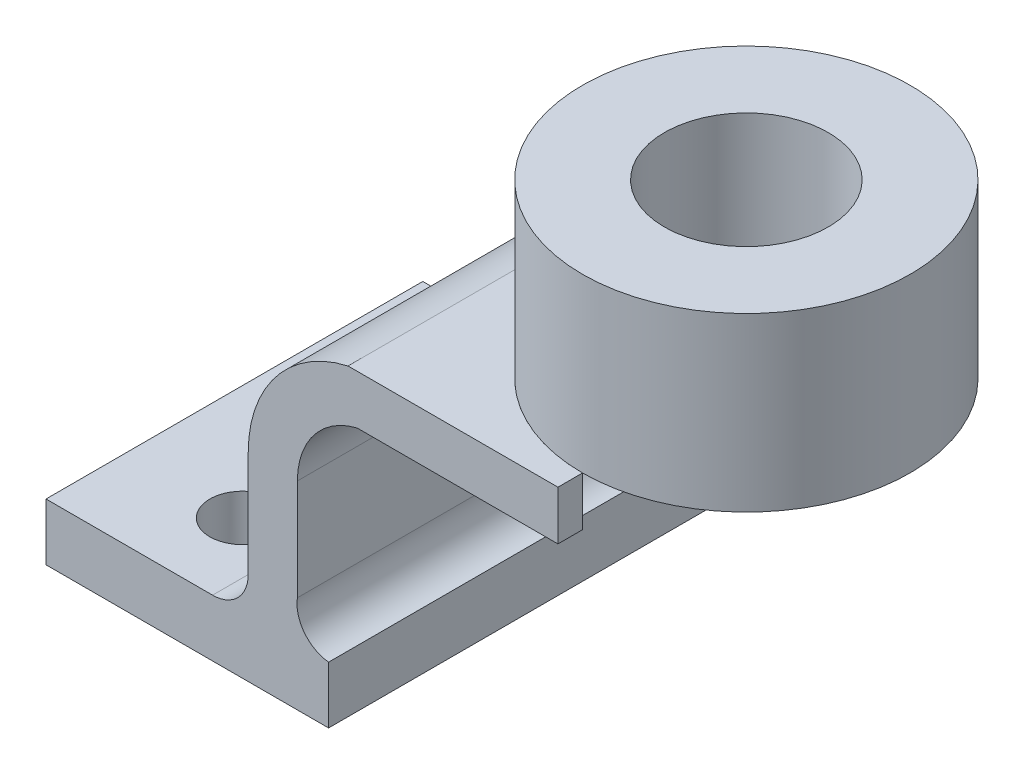
SolidWorks part; units mm, degrees
ref_plane "Front Plane" through (0, 0, 0) normal (0, 0, 1) x (1, 0, 0)
ref_plane "Top Plane" through (0, 0, 0) normal (0, 1, 0) x (1, 0, 0)
ref_plane "Right Plane" through (0, 0, 0) normal (1, 0, 0) x (0, 0, -1)
sketch "Sketch1" plane through (0, 0, 0) normal (0, 0, 1) x (1, 0, 0)
  line L0 (-83.2431, -25.4794) -> (-14.2431, -25.4794)
  line L1 (-14.2431, -25.4794) -> (-14.2431, -11.5574)
  line L2 (-83.2431, -25.4794) -> (-83.2431, -11.5574)
  line L3 (-83.2431, -11.5574) -> (-42.5734, -11.5574)
  line L7 (-7.2781, 41.4426) -> (87.9908, 41.4426)
  line L9 (-9.4954, 53.4426) -> (87.9908, 53.4426)
  line L10 (87.9908, 41.4426) -> (87.9908, 53.4426)
  line L14 (-33.867, -2.851) -> (-33.867, 22.9472)
  line L15 (-21.867, -1.7543) -> (-21.867, 22.9472)
  arc A0 (-14.2431, -11.5574) -> (-21.867, -1.7543) centre (-13.3869, -3.0255) cw
  arc A1 (-33.867, -2.851) -> (-42.5734, -11.5574) centre (-42.5734, -2.851) cw
  arc A4 (-33.867, 22.9472) -> (-9.4954, 53.4426) centre (-2.6023, 22.9472) cw
  arc A5 (-21.867, 22.9472) -> (-7.2781, 41.4426) centre (-2.8487, 22.9472) cw
  dimension "D1" = 53
extrude "Boss-Extrude4" add sketch "Sketch1" along normal blind 46 and the other way blind 46
sketch "Sketch4" plane through (0, 53.4426, 0) normal (0, 1, 0) x (1, 0, 0)
  line L0 (41.7569, 74.082) -> (41.7569, -70.2729) construction
  line L1 (-33.867, 0) -> (124.9675, 0) construction
  line L2 (-33.867, 46) -> (-33.867, -46) construction
  line L3 (87.9908, 46) -> (-9.4954, 46) construction
  line L4 (-83.2431, 46) -> (-83.2431, -46) construction
  line L5 (41.7569, 40) -> (41.7569, 45.7816)
  line L6 (41.7569, -40) -> (41.7569, -46.5044)
  circle A2 centre (41.7569, 0) radius 40
  circle A3 centre (41.7569, 0) radius 20
  circle A4 centre (41.7569, 0) radius 20
  dimension "D1" = 46
  dimension "D2" = 125
extrude "Boss-Extrude7" add sketch "Sketch4" along normal blind 42 and the other way blind 18 contours A2 A3 region at (69.2411, 53.4426, 27.4843)
sketch "Sketch5" plane through (0, 53.4426, 0) normal (0, 1, 0) x (1, 0, 0)
  line L0 (41.7569, -40) -> (41.7569, -46)
  line L1 (87.9908, -46) -> (-9.4954, -46) construction
  line L2 (41.7569, 40) -> (41.7569, 46)
  line L3 (87.9908, 46) -> (-9.4954, 46) construction
  circle A0 centre (41.7569, 0) radius 40 construction
  circle A1 centre (41.7569, 0) radius 40 construction
  circle M1 centre (41.7569, 0) radius 40
  line M2 (-9.4954, 46) -> (-9.4954, -46)
  line M3 (-9.4954, -46) -> (87.9908, -46)
  line M4 (87.9908, -46) -> (87.9908, 46)
  line M5 (87.9908, 46) -> (-9.4954, 46)
extrude "Cut-Extrude6" cut sketch "Sketch5" against normal blind 49 contours L2 L0 M1 M3 M4 M5 | M1 M2 region at (70.7692, 53.4426, 29.0123) region at (41.7569, 53.4426, 0)
sketch "Sketch3" plane through (0, -11.5574, 0) normal (0, 1, 0) x (1, 0, 0)
  line L0 (-55.2431, 62.9726) -> (-55.2431, -61.313) construction
  line L1 (-96.8317, -26) -> (-37.4756, -26) construction
  line L2 (-96.8317, 26) -> (-37.4756, 26) construction
  line L3 (-24.9355, 0) -> (112.7261, 0) construction
  line L4 (41.7569, 53.2193) -> (41.7569, -56.297) construction
  line L5 (-83.2431, 46) -> (-83.2431, -46) construction
  line L6 (-42.5734, 46) -> (-83.2431, 46) construction
  line L7 (-42.5734, -46) -> (-83.2431, -46) construction
  line L8 (41.7569, -46) -> (-9.4954, -46) construction
  line L9 (41.7569, -40) -> (41.7569, -46)
  line L10 (41.7569, 40) -> (41.7569, 46.5312)
  circle A0 centre (41.7569, 0) radius 40
  circle A1 centre (41.7569, 0) radius 20
  circle A2 centre (-55.2431, 26) radius 8
  circle A3 centre (-55.2431, -26) radius 8
  circle A4 centre (41.7569, 0) radius 20
  dimension "D1" = 28
  dimension "D2" = 20
  dimension "D3" = 20
  dimension "D4" = 125
  dimension "D5" = 46
extrude "Cut-Extrude7" cut sketch "Sketch3" against normal blind 49 contours A3 | A2 region at (-55.2431, -11.5574, -26) region at (-55.2431, -11.5574, 26)
